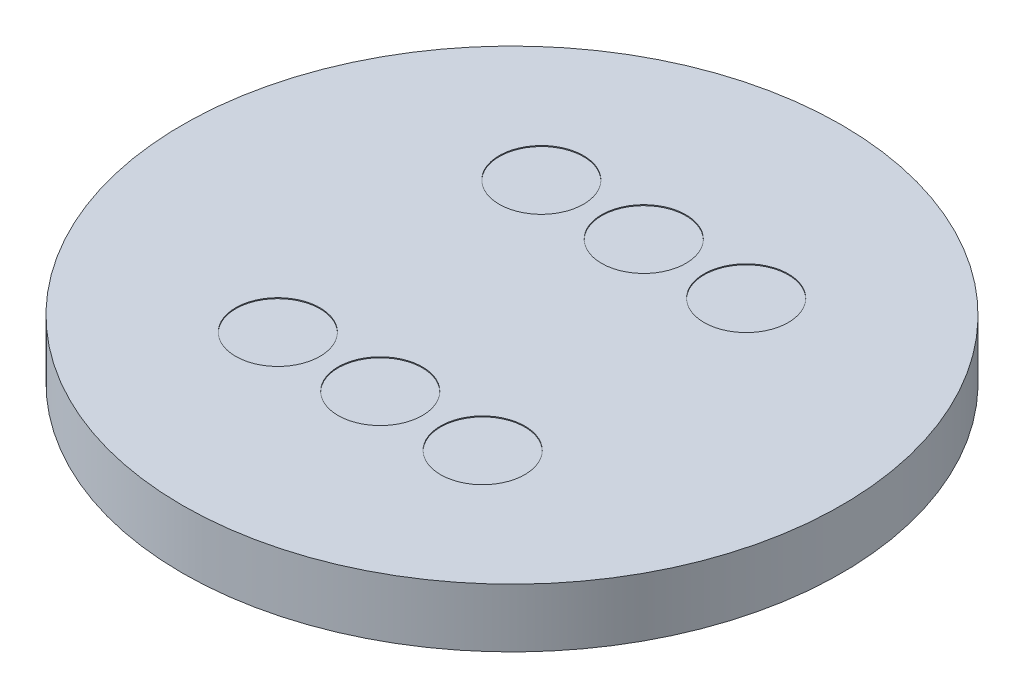
SolidWorks part; units mm, degrees
ref_plane "Front Plane" through (0, 0, 0) normal (0, 0, 1) x (1, 0, 0)
ref_plane "Top Plane" through (0, 0, 0) normal (0, 1, 0) x (1, 0, 0)
ref_plane "Right Plane" through (0, 0, 0) normal (1, 0, 0) x (0, 0, -1)
sketch "Sketch2" plane through (0, 0, 0) normal (0, 1, 0) x (1, 0, 0)
  circle A0 centre (0, 0) radius 9.271
  circle A1 centre (0, 0) radius 7.874
  circle A2 centre (0, 0) radius 5.1435
  circle A3 centre (0, 0) radius 4.826
  circle A4 centre (0, 0) radius 2.159
  circle A5 centre (0, 0) radius 1.905
  dimension "D1" = 18.542
  dimension "D2" = 15.748
  dimension "D3" = 10.287
  dimension "D4" = 9.652
  dimension "D5" = 4.318
  dimension "D6" = 3.81
extrude "Boss-Extrude1" add sketch "Sketch2" along normal blind 1.651 contours A0
extrude "Cut-Extrude1" cut sketch "Sketch2<3>" along normal blind 0.0254 contours A1 A2 | A3 A4 | A5 region at (-7.6513, 0, 0) region at (-4.6895, 0, 0) region at (0, 0, 0)
sketch "Sketch2<3>" plane through (0, 0, 0) normal (0, 1, 0) x (1, 0, 0) same geometry as "Sketch2"
sketch "Sketch3" plane through (0, 1.651, 0) normal (0, 1, 0) x (1, 0, 0)
  line L0 (2.8811, -3.7064) -> (-2.8811, -3.7064) construction
  line L1 (2.8811, 3.7064) -> (-2.8811, 3.7064) construction
  line L2 (0, -3.7064) -> (0, 3.7064) construction
  circle A0 centre (-2.8811, 3.7064) radius 1.186
  circle A1 centre (0, 0) radius 9.271
  circle A2 centre (0, 0) radius 9.271
  circle A3 centre (0, 3.7064) radius 1.186
  circle A4 centre (2.8811, 3.7064) radius 1.186
  circle A5 centre (0, -3.7064) radius 1.186
  circle A6 centre (2.8811, -3.7064) radius 1.186
  circle A7 centre (-2.8811, -3.7064) radius 1.186
  point P19 (0, -3.7064)
  point P21 (0, 3.7064)
  point P23 (0, 0)
  dimension "D1" = 0
extrude "Cut-Extrude2" cut sketch "Sketch3" against normal blind 0.0254 contours A0 | A3 | A4 | A5 | A7 | A6 region at (-2.8811, 1.651, -3.7064) region at (0, 1.651, -3.7064) region at (2.8811, 1.651, -3.7064) region at (0, 1.651, 3.7064) region at (-2.8811, 1.651, 3.7064)
